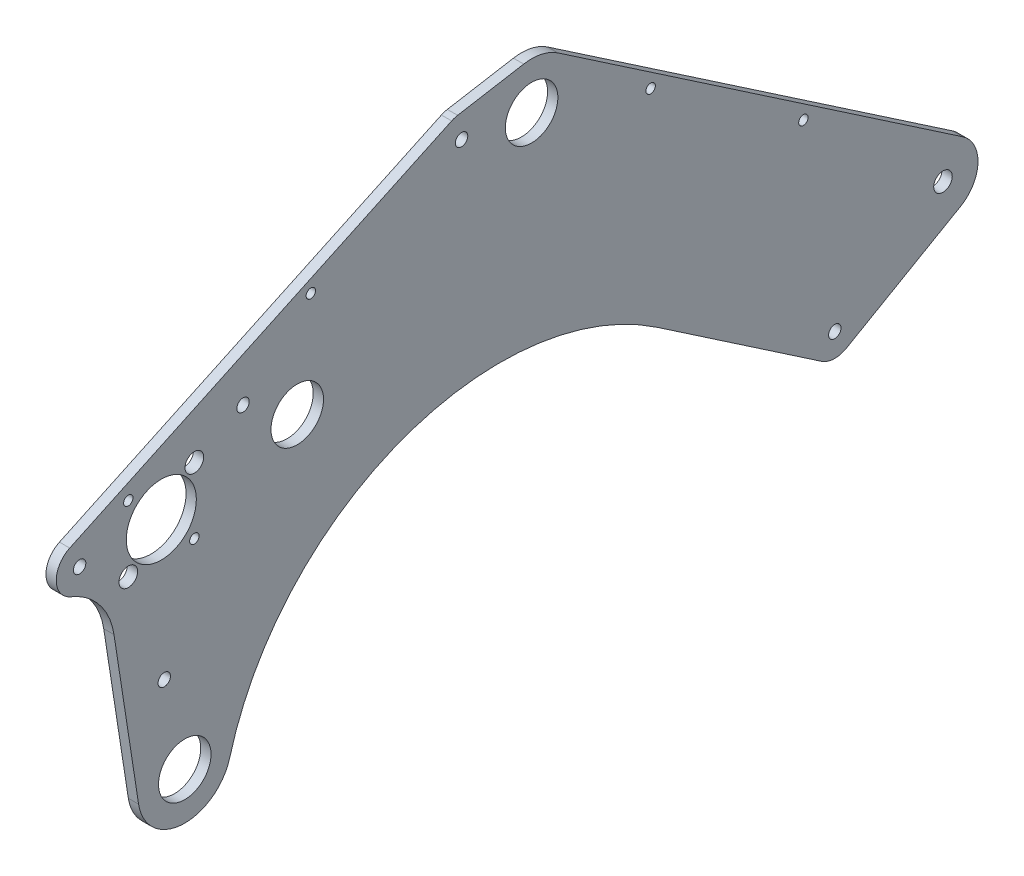
SolidWorks part; units mm, degrees
material "Acrylic (Medium-high impact)"
ref_plane "Front" through (0, 0, 0) normal (0, 0, 1) x (1, 0, 0)
ref_plane "Top" through (0, 0, 0) normal (0, 1, 0) x (1, 0, 0)
ref_plane "Right" through (0, 0, 0) normal (1, 0, 0) x (0, 0, -1)
sketch "Sketch1" plane through (0, 0, 0) normal (1, 0, 0) x (0, 0, -1)
  line L0 (-109.5375, -69.85) -> (-109.5375, -196.85)
  line L1 (-109.5375, -196.85) -> (-160.3375, -196.85)
  line L2 (-192.0875, -165.1) -> (-192.0875, -101.6)
  line L3 (-160.3375, -69.85) -> (-109.5375, -69.85)
  line L4 (-28.6872, -260.35) -> (-968.3377, -260.35) construction
  line L5 (-414.3375, -165.1) -> (-414.3375, -101.6) construction
  line L6 (-101.6, -57.15) -> (-76.2, -57.15)
  line L7 (-101.6, -57.15) -> (-101.6, -82.55)
  line L8 (-101.6, -82.55) -> (-76.2, -82.55)
  line L9 (-76.2, -57.15) -> (-76.2, -82.55)
  line L10 (-160.3375, 152.4) -> (-109.5375, 152.4) construction
  line L11 (-412.4442, -70.6452) -> (-160.3375, -101.6) construction
  line L12 (-351.247, 65.9398) -> (-160.3375, -101.6) construction
  line L13 (-223.7678, 144.3524) -> (-160.3375, -101.6) construction
  line L14 (-430.6959, -62.4675) -> (-369.4987, 74.1175)
  line L15 (-332.9953, 57.762) -> (-394.1925, -78.8229)
  line L16 (-361.7254, 82.9751) -> (-234.2463, 161.3877)
  line L17 (-109.5375, -69.85) -> (-109.5375, 357.098) construction
  line L18 (-213.2894, 127.3171) -> (-340.7685, 48.9045)
  line L19 (-515.9375, 289.2974) -> (-515.9375, -104.2984) construction
  line L20 (-405.2884, 55.4141) -> (-392.5489, -68.6015)
  line L21 (-432.3395, -72.6889) -> (-445.079, 51.3266)
  circle A0 centre (0, 0) radius 5.0419
  circle A1 centre (-412.4442, -70.6452) radius 11.557
  circle A2 centre (-351.247, 65.9398) radius 11.557
  circle A3 centre (-223.7678, 144.3524) radius 11.557
  arc A4 (-160.3375, -196.85) -> (-192.0875, -165.1) centre (-160.3375, -165.1) cw
  arc A5 (-192.0875, -101.6) -> (-160.3375, -69.85) centre (-160.3375, -101.6) cw
  circle A6 centre (-312.1509, -135.302) radius 120.65
  arc A7 (-414.3375, -101.6) -> (-160.3375, 152.4) centre (-160.3375, -101.6) cw construction
  circle A12 centre (-425.1837, 53.3704) radius 31.75
  arc A15 (-394.1925, -78.8229) -> (-430.6959, -62.4675) centre (-412.4442, -70.6452) cw
  arc A16 (-369.4987, 74.1175) -> (-332.9953, 57.762) centre (-351.247, 65.9398) cw
  arc A17 (-340.7685, 48.9045) -> (-361.7254, 82.9751) centre (-351.247, 65.9398) cw
  arc A18 (-234.2463, 161.3877) -> (-213.2894, 127.3171) centre (-223.7678, 144.3524) cw
  arc A19 (-445.079, 51.3266) -> (-405.2884, 55.4141) centre (-425.1837, 53.3704) cw
  arc A20 (-392.5489, -68.6015) -> (-432.3395, -72.6889) centre (-412.4442, -70.6452) cw
  point P45 (-326.286, -120.65)
  point P46 (-312.1509, -135.302)
  circle B0 centre (-223.7678, 144.3524) radius 20
  circle B1 centre (-351.247, 65.9398) radius 20
  circle B2 centre (-412.4442, -70.6452) radius 20
  circle B3 centre (-425.1837, 53.3704) radius 20
  dimension "D1" = 10.0838
  dimension "D2" = 23.114
  dimension "D4" = 31.75
  dimension "D10" = 241.3
  dimension "D19" = 63.5
  dimension "D26" = 70.6452
  dimension "D27" = 412.4442
  dimension "D3" = 127
  dimension "D5" = 82.55
  dimension "D6" = 190.5
  dimension "D7" = 25.4
  dimension "D8" = 7.9375
  dimension "D9" = 203.2
  dimension "D12" = 101.6
  dimension "D13" = 57.15
  dimension "D14" = 34.27
  dimension "D15" = 34.269
  dimension "D16" = 7
  dimension "D24" = 406.4
  dimension "D21" = 30
  dimension "D11" = 222.25
sketch_block_instance "Block1-1"
sketch_block "Block1" parameters "D1"=40
sketch_block_instance "Block2-1"
sketch_block "Block2"
sketch_block_instance "Block3-1"
sketch_block "Block3"
sketch_block_instance "Block4-1"
sketch_block "Block4" parameters "D1"=40
other "Belt1"
other "Belt2"
other "Belt4"
sketch "Sketch3" plane through (0, 0, 0) normal (1, 0, 0) x (0, 0, -1)
  line L0 (-412.4442, -70.6452) -> (0, 0) construction
  line L1 (0, 0) -> (-58.8496, -41.2069) construction
  line L2 (0, 0) -> (-70.6452, 412.4442) construction
  line L3 (0, 0) -> (-41.2069, 58.8496) construction
  line L4 (-58.8496, -41.2069) -> (-64.0291, -10.9672) construction
  line L5 (-41.2069, 58.8496) -> (-10.9672, 64.0291) construction
  line L6 (-41.2069, 58.8496) -> (-58.8496, -41.2069)
  line L7 (-3.1649, 274.5963) -> (-41.2069, 58.8496)
  line L8 (0, 0) -> (144.3524, 223.7678) construction
  line L9 (0, 0) -> (-223.7678, 144.3524) construction
  line L10 (-223.7678, 144.3524) -> (-193.3694, -33.1211) construction
  line L11 (144.3524, 223.7678) -> (-33.1211, 193.3694) construction
  circle A0 centre (-70.6452, 412.4442) radius 25.4
  point P9 (0, 0)
  dimension "D1" = 50.8
  dimension "D2" = 90
  dimension "D3" = 101.6
  dimension "D4" = 219.075
  dimension "D5" = 80
sketch "Sketch2" plane through (0, 0, 0) normal (1, 0, 0) x (0, 0, -1)
  line L0 (-437.5463, -74.5243) -> (-450.9257, 12.0539)
  line L1 (-475.0213, 64.8709) -> (-267.2555, 162.203)
  line L2 (-412.4442, -70.6452) -> (-412.4442, 0) construction
  line L4 (10.7056, 15.7573) -> (-209.4937, 165.3622)
  line L7 (-65.9866, -51.7118) -> (-155.1924, 8.8953)
  line L10 (-52.5132, -52.2133) -> (9.5046, -16.5096)
  line L11 (-264.015, 163.2196) -> (-228.0621, 169.3868)
  line L13 (-443.1442, 35.4098) -> (-407.2231, 71.3309) construction
  line L14 (-443.1442, 71.3309) -> (-407.2231, 35.4098) construction
  circle A0 centre (-223.7678, 144.3524) radius 14.2875
  circle A1 centre (-351.247, 65.9398) radius 14.2875
  circle A2 centre (-412.4442, -70.6452) radius 14.2875
  circle A3 centre (-425.1837, 53.3704) radius 19.05
  circle A9 centre (0, 0) radius 5.0419 construction
  circle A10 centre (0, 0) radius 5.0419
  arc A13 (-437.5463, -74.5243) -> (-387.929, -77.2906) centre (-412.4442, -70.6452) ccw
  arc A16 (9.5046, -16.5096) -> (10.7056, 15.7573) centre (0, 0) ccw
  arc A18 (-155.1924, 8.8953) -> (-387.929, -77.2906) centre (-240.8373, -117.1631) ccw
  circle A19 centre (-58.8496, -41.2069) radius 3.3782
  circle A22 centre (-261.8678, 150.7024) radius 3.3782
  arc A23 (-267.2555, 162.203) -> (-264.015, 163.2196) centre (-261.8678, 150.7024) cw
  circle A24 centre (-223.7678, 144.3524) radius 25.4 construction
  circle A27 centre (-407.2231, 71.3309) radius 5.08
  circle A28 centre (-443.1442, 71.3309) radius 2.5527
  circle A29 centre (-443.1442, 35.4098) radius 5.08
  circle A30 centre (-407.2231, 35.4098) radius 2.5527
  circle A31 centre (-425.1837, 53.3704) radius 25.4 construction
  circle A32 centre (-469.6337, 53.3704) radius 3.3782
  arc A34 (-475.0213, 64.8709) -> (-474.3699, 41.5866) centre (-469.6337, 53.3704) ccw
  arc A35 (-474.3699, 41.5866) -> (-450.9257, 12.0539) centre (-488.5787, 6.2352) cw
  circle A37 centre (-425.1837, 53.3704) radius 31.75 construction
  circle A38 centre (-469.6337, 53.3704) radius 7.9375 construction
  circle A39 centre (-423.5962, -22.8296) radius 3.3782
  circle A40 centre (-423.5962, -22.8296) radius 7.9375 construction
  circle A41 centre (-380.7337, 85.1204) radius 3.3782
  arc A42 (-65.9866, -51.7118) -> (-52.5132, -52.2133) centre (-58.8496, -41.2069) ccw
  arc A43 (-228.0621, 169.3868) -> (-209.4937, 165.3622) centre (-223.7678, 144.3524) cw
  dimension "D1" = 28.575
  dimension "D2" = 38.1
  dimension "D3" = 6.35
  dimension "D4" = 50.8
  dimension "D5" = 12.7
  dimension "D6" = 38.1
  dimension "D7" = 19.05
  dimension "D8" = 152.4
  dimension "D10" = 6.7564
  dimension "D11" = 6.7564
  dimension "D12" = 15.875
  dimension "D13" = 12.7
  dimension "D17" = 15.875
  dimension "D18" = 5.1054
  dimension "D19" = 10.16
  dimension "D20" = 50.8
  dimension "D21" = 25.4
  dimension "D22" = 38.1
  dimension "D23" = 1.5875
  dimension "D16" = 44.45
  dimension "D15" = 31.75
  dimension "D24" = 76.2
  dimension "D25" = 44.45
  dimension "D9" = 12.7
extrude "Boss-Extrude1" add sketch "Sketch2" along normal blind 5.588
sketch "Sketch4" plane through (5.588, 0, 0) normal (1, 0, 0) x (0, 0, -1)
  line L0 (-351.247, 65.9398) -> (-223.7678, 144.3524) construction
  line L1 (-267.2555, 162.203) -> (-475.0213, 64.8709) construction
  line L3 (-343.8725, 119.2979) -> (-435.8771, 76.1966) construction
  line L4 (-435.8771, 76.1966) -> (-425.1837, 53.3704) construction
  line L6 (10.7056, 15.7573) -> (-209.4937, 165.3622) construction
  line L11 (-242.0814, 179.8255) -> (-159.0086, 123.3853) construction
  line L12 (-159.0086, 123.3853) -> (-75.9357, 66.9451) construction
  line L13 (-75.9357, 66.9451) -> (7.1371, 10.5049) construction
  line L14 (-242.0814, 179.8255) -> (-261.8678, 150.7024) construction
  line L15 (0, 0) -> (7.1371, 10.5049) construction
  circle A4 centre (-343.8725, 119.2979) radius 2.5527
  circle A5 centre (-159.0086, 123.3853) radius 2.5527
  circle A6 centre (-75.9357, 66.9451) radius 2.5527
  dimension "D1" = 6.35
  dimension "D2" = 5.1054
  dimension "D3" = 101.6
  dimension "D6" = 6.35
extrude "Cut-Extrude1" cut sketch "Sketch4" against normal through all
